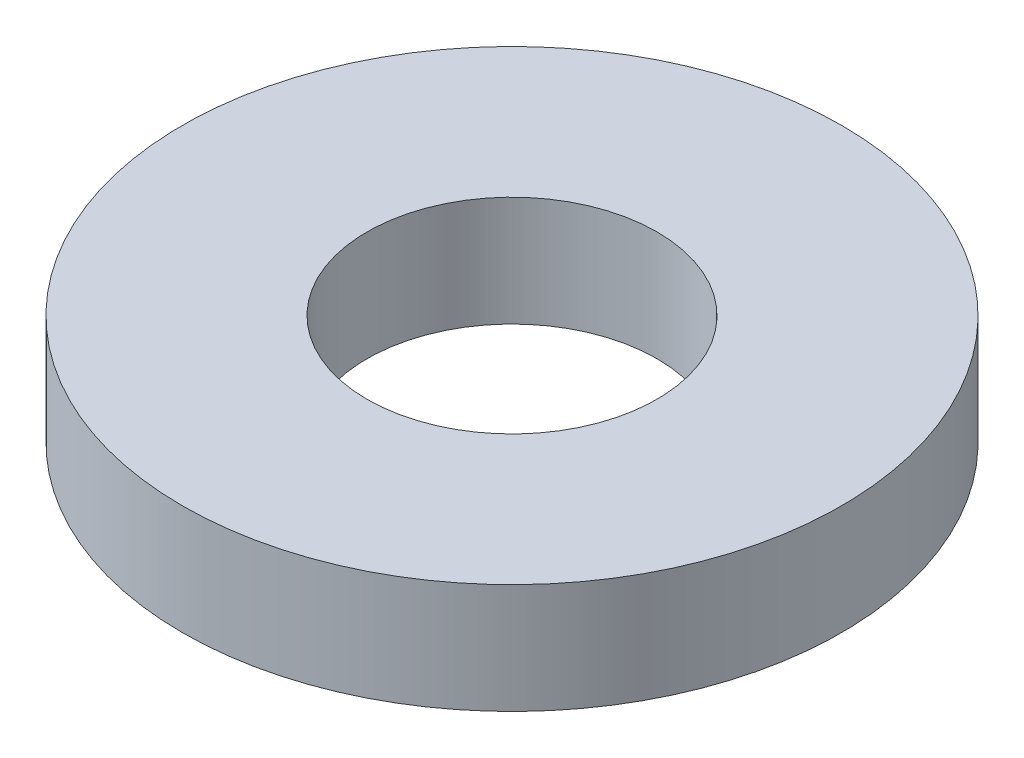
SolidWorks part; units mm, degrees
material "Nylon 101"
ref_plane "Front Plane" through (0, 0, 0) normal (0, 0, 1) x (1, 0, 0)
ref_plane "Top Plane" through (0, 0, 0) normal (0, 1, 0) x (1, 0, 0)
ref_plane "Right Plane" through (0, 0, 0) normal (1, 0, 0) x (0, 0, -1)
other "1/32"
sketch "Sketch1" plane through (0, 0, 0) normal (0, 1, 0) x (1, 0, 0)
  circle A0 centre (0, 0) radius 2.0955
  circle A1 centre (0, 0) radius 4.7625
  dimension "D1" = 4.191
  dimension "D2" = 9.525
extrude "Boss-Extrude1" add sketch "Sketch1" along normal blind 1.5875
